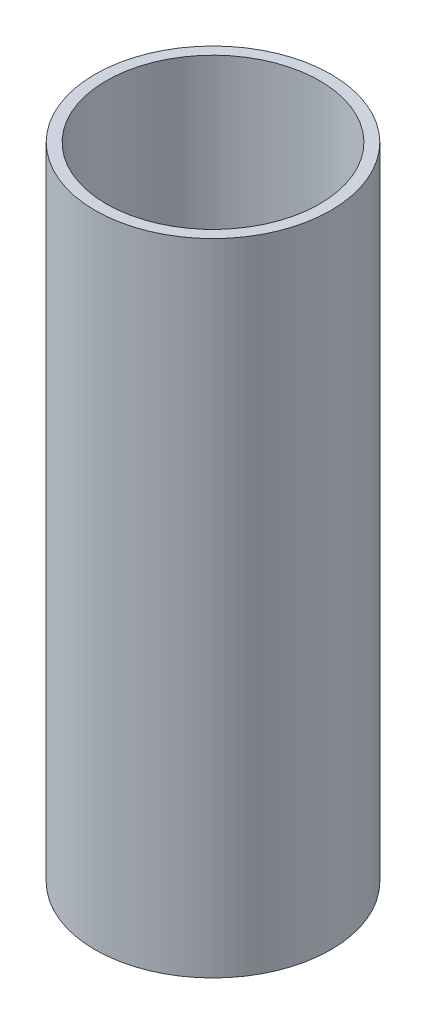
SolidWorks part; units mm, degrees
ref_plane "Front Plane" through (0, 0, 0) normal (0, 0, 1) x (1, 0, 0)
ref_plane "Top Plane" through (0, 0, 0) normal (0, 1, 0) x (1, 0, 0)
ref_plane "Right Plane" through (0, 0, 0) normal (1, 0, 0) x (0, 0, -1)
sketch "Sketch1" plane through (0, 0, 0) normal (0, 1, 0) x (1, 0, 0)
  circle A0 centre (0, 0) radius 21
  circle A1 centre (0, 0) radius 19
extrude "Boss-Extrude1" add sketch "Sketch1" along normal blind 49
extrude "Boss-Extrude2" add sketch "Sketch1<2>" along normal blind 114
sketch "Sketch1<2>" plane through (0, 0, 0) normal (0, 1, 0) x (1, 0, 0) same geometry as "Sketch1"
